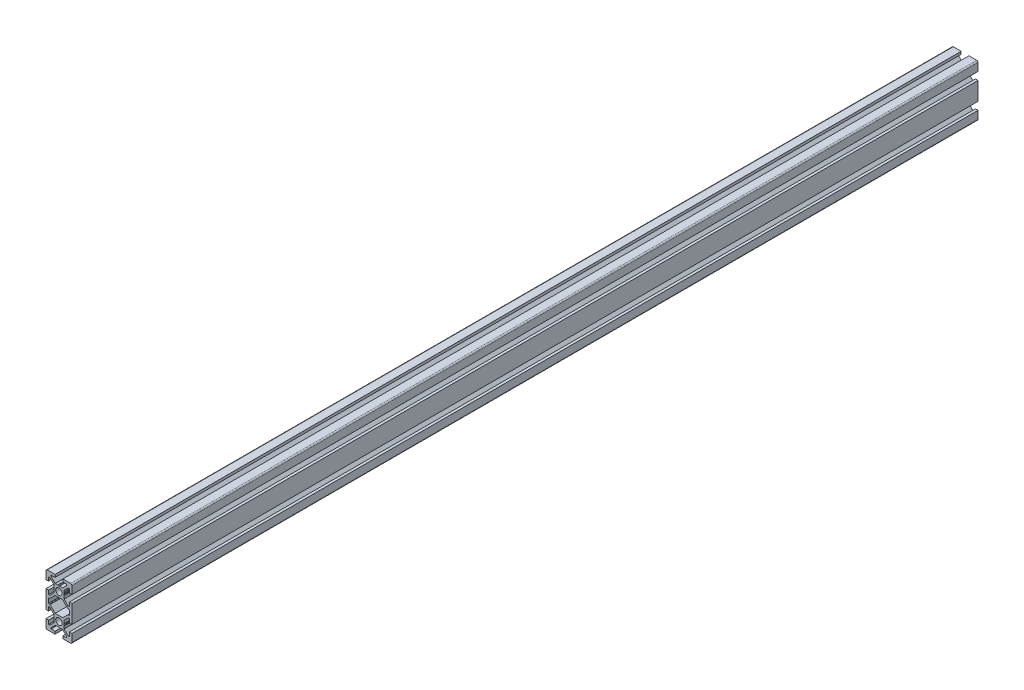
SolidWorks part; units mm, degrees
material "1060 Alloy"
ref_plane "Front Plane" through (0, 0, 0) normal (0, 0, 1) x (1, 0, 0)
ref_plane "Top Plane" through (0, 0, 0) normal (0, 1, 0) x (1, 0, 0)
ref_plane "Right Plane" through (0, 0, 0) normal (1, 0, 0) x (0, 0, -1)
ref_plane "Plane1" through (0, 0, -600) normal (0, 0, -1) x (-1, 0, 0)
sketch "Sketch1" plane through (0, 0, -600) normal (0, 0, -1) x (-1, 0, 0)
  line L0 (8, 1.7) -> (8, -1.7)
  line L1 (7.7, -2) -> (7.0636, -2)
  line L2 (6.8515, -2.0879) -> (2.9393, -6)
  line L3 (2.9393, -6) -> (-2.9393, -6)
  line L4 (-2.9393, -6) -> (-6.8515, -2.0879)
  line L5 (-7.0636, -2) -> (-7.7, -2)
  line L6 (-8, -1.7) -> (-8, 1.7)
  line L7 (-7.7, 2) -> (-7.0636, 2)
  line L8 (-6.8515, 2.0879) -> (-2.9393, 6)
  line L9 (-2.9393, 6) -> (2.9393, 6)
  line L10 (2.9393, 6) -> (6.8515, 2.0879)
  line L11 (7.0636, 2) -> (7.7, 2)
  line L12 (10, -7) -> (10, 7)
  line L13 (10, 7) -> (8, 7)
  line L14 (8, 7) -> (8, 4)
  line L15 (8, 4) -> (7.0607, 4)
  line L16 (7.0607, 4) -> (4, 7.0607)
  line L17 (4, 7.0607) -> (4, 7.5)
  line L18 (4, 7.5) -> (3.751, 8.7811)
  line L19 (3.751, 8.7811) -> (3.933, 9.0964)
  line L20 (3.933, 9.5964) -> (3.7, 10)
  line L21 (3.7, 10) -> (3.933, 10.4036)
  line L22 (4, 10.6536) -> (4, 12.9393)
  line L23 (4, 12.9393) -> (7.0607, 16)
  line L24 (7.0607, 16) -> (8, 16)
  line L25 (8, 16) -> (8, 13)
  line L26 (8, 13) -> (10, 13)
  line L27 (10, 13) -> (10, 19)
  line L28 (9, 20) -> (3, 20)
  line L29 (3, 20) -> (3, 18)
  line L30 (3, 18) -> (6, 18)
  line L31 (6, 18) -> (6, 17.0607)
  line L32 (6, 17.0607) -> (2.9393, 14)
  line L33 (2.9393, 14) -> (2.5, 14)
  line L34 (2.5, 14) -> (1.2189, 13.751)
  line L35 (1.2189, 13.751) -> (0.9036, 13.933)
  line L36 (0.4036, 13.933) -> (0, 13.7)
  line L37 (0, 13.7) -> (-0.4036, 13.933)
  line L38 (-0.6536, 14) -> (-2.9393, 14)
  line L39 (-2.9393, 14) -> (-6, 17.0607)
  line L40 (-6, 17.0607) -> (-6, 18)
  line L41 (-6, 18) -> (-3, 18)
  line L42 (-3, 18) -> (-3, 20)
  line L43 (-3, 20) -> (-9, 20)
  line L44 (-10, 19) -> (-10, 13)
  line L45 (-10, 13) -> (-8, 13)
  line L46 (-8, 13) -> (-8, 16)
  line L47 (-8, 16) -> (-7.0607, 16)
  line L48 (-7.0607, 16) -> (-4, 12.9393)
  line L49 (-4, 12.9393) -> (-4, 12.5)
  line L50 (-4, 12.5) -> (-3.751, 11.2189)
  line L51 (-3.751, 11.2189) -> (-3.933, 10.9036)
  line L52 (-3.933, 10.4036) -> (-3.7, 10)
  line L53 (-3.7, 10) -> (-3.933, 9.5964)
  line L54 (-4, 9.3464) -> (-4, 7.0607)
  line L55 (-4, 7.0607) -> (-7.0607, 4)
  line L56 (-7.0607, 4) -> (-8, 4)
  line L57 (-8, 4) -> (-8, 7)
  line L58 (-8, 7) -> (-10, 7)
  line L59 (-10, 7) -> (-10, -7)
  line L60 (-10, -7) -> (-8, -7)
  line L61 (-8, -7) -> (-8, -4)
  line L62 (-8, -4) -> (-7.0607, -4)
  line L63 (-7.0607, -4) -> (-4, -7.0607)
  line L64 (-4, -7.0607) -> (-4, -9.3464)
  line L65 (-3.933, -9.5964) -> (-3.7, -10)
  line L66 (-3.7, -10) -> (-3.933, -10.4036)
  line L67 (-3.933, -10.9036) -> (-3.751, -11.2189)
  line L68 (-3.751, -11.2189) -> (-4, -12.5)
  line L69 (-4, -12.5) -> (-4, -12.9393)
  line L70 (-4, -12.9393) -> (-7.0607, -16)
  line L71 (-7.0607, -16) -> (-8, -16)
  line L72 (-8, -16) -> (-8, -13)
  line L73 (-8, -13) -> (-10, -13)
  line L74 (-10, -13) -> (-10, -19)
  line L75 (-9, -20) -> (-3, -20)
  line L76 (-3, -20) -> (-3, -18)
  line L77 (-3, -18) -> (-6, -18)
  line L78 (-6, -18) -> (-6, -17.0607)
  line L79 (-6, -17.0607) -> (-2.9393, -14)
  line L80 (-2.9393, -14) -> (-0.6536, -14)
  line L81 (-0.4036, -13.933) -> (0, -13.7)
  line L82 (0, -13.7) -> (0.4036, -13.933)
  line L83 (0.9036, -13.933) -> (1.2189, -13.751)
  line L84 (1.2189, -13.751) -> (2.5, -14)
  line L85 (2.5, -14) -> (2.9393, -14)
  line L86 (2.9393, -14) -> (6, -17.0607)
  line L87 (6, -17.0607) -> (6, -18)
  line L88 (6, -18) -> (3, -18)
  line L89 (3, -18) -> (3, -20)
  line L90 (3, -20) -> (9, -20)
  line L91 (10, -19) -> (10, -13)
  line L92 (10, -13) -> (8, -13)
  line L93 (8, -13) -> (8, -16)
  line L94 (8, -16) -> (7.0607, -16)
  line L95 (7.0607, -16) -> (4, -12.9393)
  line L96 (4, -12.9393) -> (4, -10.6536)
  line L97 (3.933, -10.4036) -> (3.7, -10)
  line L98 (3.7, -10) -> (3.933, -9.5964)
  line L99 (3.933, -9.0964) -> (3.751, -8.7811)
  line L100 (3.751, -8.7811) -> (4, -7.5)
  line L101 (4, -7.5) -> (4, -7.0607)
  line L102 (4, -7.0607) -> (7.0607, -4)
  line L103 (7.0607, -4) -> (8, -4)
  line L104 (8, -4) -> (8, -7)
  line L105 (8, -7) -> (10, -7)
  circle A0 centre (0, -10) radius 2.5
  circle A1 centre (0, 10) radius 2.5
  arc A2 (7.7, 2) -> (8, 1.7) centre (7.7, 1.7) cw
  arc A3 (8, -1.7) -> (7.7, -2) centre (7.7, -1.7) cw
  arc A4 (7.0636, -2) -> (6.8515, -2.0879) centre (7.0636, -2.3) ccw
  arc A5 (-6.8515, -2.0879) -> (-7.0636, -2) centre (-7.0636, -2.3) ccw
  arc A6 (-7.7, -2) -> (-8, -1.7) centre (-7.7, -1.7) cw
  arc A7 (-8, 1.7) -> (-7.7, 2) centre (-7.7, 1.7) cw
  arc A8 (-7.0636, 2) -> (-6.8515, 2.0879) centre (-7.0636, 2.3) ccw
  arc A9 (6.8515, 2.0879) -> (7.0636, 2) centre (7.0636, 2.3) ccw
  arc A10 (3.933, 9.0964) -> (3.933, 9.5964) centre (3.5, 9.3464) ccw
  arc A11 (3.933, 10.4036) -> (4, 10.6536) centre (3.5, 10.6536) ccw
  arc A12 (10, 19) -> (9, 20) centre (9, 19) ccw
  arc A13 (0.9036, 13.933) -> (0.4036, 13.933) centre (0.6536, 13.5) ccw
  arc A14 (-0.4036, 13.933) -> (-0.6536, 14) centre (-0.6536, 13.5) ccw
  arc A15 (-9, 20) -> (-10, 19) centre (-9, 19) ccw
  arc A16 (-3.933, 10.9036) -> (-3.933, 10.4036) centre (-3.5, 10.6536) ccw
  arc A17 (-3.933, 9.5964) -> (-4, 9.3464) centre (-3.5, 9.3464) ccw
  arc A18 (-4, -9.3464) -> (-3.933, -9.5964) centre (-3.5, -9.3464) ccw
  arc A19 (-3.933, -10.4036) -> (-3.933, -10.9036) centre (-3.5, -10.6536) ccw
  arc A20 (-10, -19) -> (-9, -20) centre (-9, -19) ccw
  arc A21 (-0.6536, -14) -> (-0.4036, -13.933) centre (-0.6536, -13.5) ccw
  arc A22 (0.4036, -13.933) -> (0.9036, -13.933) centre (0.6536, -13.5) ccw
  arc A23 (9, -20) -> (10, -19) centre (9, -19) ccw
  arc A24 (4, -10.6536) -> (3.933, -10.4036) centre (3.5, -10.6536) ccw
  arc A25 (3.933, -9.5964) -> (3.933, -9.0964) centre (3.5, -9.3464) ccw
  dimension "D1" = 5
  dimension "D3" = 0.3
  dimension "D4" = 0.3
  dimension "D5" = 0.3
  dimension "D6" = 0.3
  dimension "D7" = 0.3
  dimension "D8" = 0.3
  dimension "D9" = 0.3
  dimension "D10" = 0.5
  dimension "D11" = 0.5
  dimension "D12" = 1
  dimension "D13" = 0.5
  dimension "D14" = 0.5
  dimension "D15" = 1
  dimension "D16" = 0.5
  dimension "D17" = 0.5
  dimension "D18" = 0.5
  dimension "D19" = 0.5
  dimension "D20" = 0.4036
  dimension "D21" = 0.5
  dimension "D22" = 0.5
  dimension "D23" = 1
  dimension "D24" = 0.5
  dimension "D25" = 0.5
  dimension "D26" = 0.4036
  dimension "D27" = 0.6536
  dimension "D28" = 0.6536
  dimension "D29" = 0.9036
  dimension "D30" = 0.9036
  dimension "D31" = 1.2189
  dimension "D32" = 1.2189
  dimension "D33" = 2.5
  dimension "D34" = 2.5
  dimension "D35" = 2.9393
  dimension "D36" = 2.9393
  dimension "D37" = 3
  dimension "D38" = 3.5
  dimension "D39" = 6
  dimension "D40" = 6.8515
  dimension "D41" = 3.7
  dimension "D42" = 3.7
  dimension "D43" = 3.751
  dimension "D44" = 3.751
  dimension "D45" = 3.933
  dimension "D46" = 3.933
  dimension "D47" = 6.8515
  dimension "D48" = 7.0607
  dimension "D49" = 7.0607
  dimension "D50" = 7.0636
  dimension "D51" = 7.0636
  dimension "D52" = 8
  dimension "D53" = 10
  dimension "D54" = 3
  dimension "D55" = 4
  dimension "D56" = 6
  dimension "D57" = 6.8515
  dimension "D58" = 6.8515
  dimension "D59" = 7.0607
  dimension "D60" = 7.0607
  dimension "D61" = 0.4036
  dimension "D62" = 0.4036
  dimension "D63" = 0.6536
  dimension "D64" = 0.6536
  dimension "D65" = 2.9393
  dimension "D66" = 2.9393
  dimension "D67" = 8
  dimension "D68" = 2
  dimension "D69" = 3.5
  dimension "D70" = 3.5
  dimension "D71" = 3.7
  dimension "D72" = 3.7
  dimension "D73" = 3.751
  dimension "D74" = 3.751
  dimension "D75" = 3.933
  dimension "D76" = 3.933
  dimension "D77" = 4
  dimension "D78" = 6
  dimension "D79" = 7
  dimension "D80" = 7.0607
  dimension "D81" = 7.0607
  dimension "D82" = 7.5
  dimension "D83" = 8.7811
  dimension "D84" = 9.0964
  dimension "D85" = 9.3464
  dimension "D86" = 9.3464
  dimension "D87" = 9.5964
  dimension "D88" = 9.5964
  dimension "D89" = 10.4036
  dimension "D90" = 12.5
  dimension "D91" = 13
  dimension "D92" = 13.5
  dimension "D93" = 13.5
  dimension "D94" = 18
  dimension "D95" = 20
  dimension "D96" = 2
  dimension "D97" = 4
  dimension "D98" = 6
  dimension "D99" = 7
  dimension "D100" = 7.0607
  dimension "D101" = 7.0607
  dimension "D102" = 7.5
  dimension "D103" = 8.7811
  dimension "D104" = 9.0964
  dimension "D105" = 9.3464
  dimension "D106" = 9.3464
  dimension "D107" = 9.5964
  dimension "D108" = 9.5964
  dimension "D109" = 10.4036
  dimension "D110" = 12.5
  dimension "D111" = 13
  dimension "D112" = 18
extrude "Boss-Extrude1" add sketch "Sketch1" against normal blind 700
sketch "Sketch2" plane through (-10, 0, 0) normal (-1, 0, 0) x (0, 0, 1)
  line L0 (100, 13) -> (100, 7) construction
  line L1 (100, 10) -> (90, 10) construction
  line L2 (100, -7) -> (100, -13) construction
  line L3 (100, -10) -> (90, -10) construction
  circle A0 centre (90, 10) radius 2
  circle A1 centre (90, -10) radius 2
  dimension "D3" = 4
  dimension "D4" = 4
  dimension "D1" = 10
  dimension "D2" = 10
extrude "Cut-Extrude1" cut sketch "Sketch2" against normal through all
ref_plane "Plane2" through (0, 0, -250) normal (0, 0, 1) x (1, 0, 0)
mirror "Mirror1" about plane through (0, 0, -250) normal (0, 0, 1) of "Cut-Extrude1"
